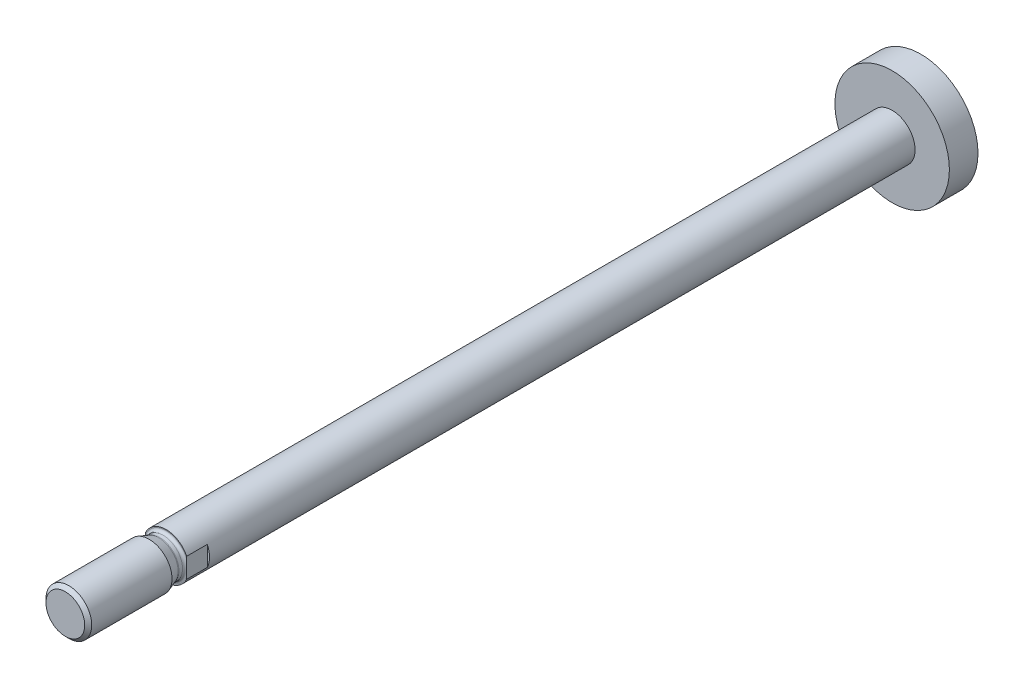
SolidWorks part; units mm, degrees
ref_plane "Ebene vorne" through (0, 0, 0) normal (0, 0, 1) x (1, 0, 0)
ref_plane "Ebene oben" through (0, 0, 0) normal (0, 1, 0) x (1, 0, 0)
ref_plane "Ebene rechts" through (0, 0, 0) normal (1, 0, 0) x (0, 0, -1)
sketch "Skizze1" plane through (0, 0, 0) normal (1, 0, 0) x (0, 0, -1)
  line L0 (-6, 0) -> (-6, 5)
  line L1 (-6, 5) -> (152.6, 5)
  line L2 (152.6, 5) -> (152.6, 12.5)
  line L3 (152.6, 12.5) -> (158.85, 12.5)
  line L4 (158.85, 12.5) -> (158.85, 0)
  line L5 (158.85, 0) -> (-6, 0)
  line L6 (158.85, 0) -> (-6, 0) construction
revolve "Rotation1" add sketch "Skizze1" angle 360 about L6 reverse direction yes
sketch "Skizze2" plane through (0, 0, 0) normal (1, 0, 0) x (0, 0, -1)
  line L0 (-28, 0) -> (-28, 4.233)
  line L1 (-28, 4.233) -> (-27.233, 5)
  line L2 (-27.233, 5) -> (-9.698, 5)
  line L3 (-9.698, 5) -> (-7.5994, 4.2362)
  line L4 (-7.3942, 4.2) -> (-6.6, 4.2)
  line L5 (-6, 4.8) -> (-6, 5)
  line L6 (-6, 5) -> (-5, 5)
  line L7 (-5, 5) -> (-5, 0)
  line L8 (-5, 0) -> (-28, 0)
  line L9 (-5, 0) -> (-28, 0) construction
  arc A0 (-7.5994, 4.2362) -> (-7.3942, 4.2) centre (-7.3942, 4.8) ccw
  arc A1 (-6.6, 4.2) -> (-6, 4.8) centre (-6.6, 4.8) ccw
revolve "Rotation2" add sketch "Skizze2" angle 360 about L9 reverse direction yes
cosmetic thread "Gewindedarstellung1" parameters "D1"=18.302, "D2"=8.466
ref_plane "Ebene1" through (0, 0, 6) normal (0, 0, 1) x (1, 0, 0)
ref_plane "Ebene2" through (0, 0, 1.5) normal (0, 0, 1) x (1, 0, 0)
sketch "Skizze3" plane through (0, 0, 1.5) normal (0, 0, 1) x (1, 0, 0)
  line L0 (-9, 18) -> (-9, -9)
  line L1 (-9, -9) -> (-4.5, -9)
  line L2 (-4.5, -9) -> (-4.5, 9)
  line L3 (-4.5, 9) -> (4.5, 9)
  line L4 (4.5, 9) -> (4.5, -9)
  line L5 (4.5, -9) -> (9, -9)
  line L6 (9, -9) -> (9, 18)
  line L7 (9, 18) -> (-9, 18)
extrude "Schnitt-Linear austragen1" cut sketch "Skizze3" along normal blind 5.5
ref_plane "Ebene3" through (0, 0, -319.5) normal (0, 0, 1) x (1, 0, 0)
ref_plane "Ebene4" through (0, 0, 17.667) normal (0, 0, 1) x (1, 0, 0)
ref_plane "Ebene5" through (0, 0, 15) normal (0, 0, 1) x (1, 0, 0)
ref_plane "FDT_KSAUFSATZ XY" through (0, 0, 15) normal (0, 0, 1) x (1, 0, 0)
ref_plane "FDT_KSAUFSATZ XZ" through (0, 0, 0) normal (0, 1, 0) x (1, 0, 0)
ref_plane "FDT_KSAUFSATZ YZ" through (0, 0, 0) normal (-1, 0, 0) x (0, 0, 1)
ref_axis "FDT_KSAUFSATZ X" through (80.9, 0, 15) along (-1, 0, 0)
ref_axis "FDT_KSAUFSATZ Y" through (0, 50, 15) along (0, -1, 0)
ref_axis "FDT_KSAUFSATZ Z" through (0, 0, 80.9) along (0, 0, -1)
sketch3d "FDT_KSAUFSATZ"
  point P0 (0, 0, 15)
ref_plane "FDT_NUT XY" through (0, 0, 15) normal (0, 0, 1) x (1, 0, 0)
ref_plane "FDT_NUT XZ" through (0, 0, 0) normal (0, 1, 0) x (1, 0, 0)
ref_plane "FDT_NUT YZ" through (0, 0, 0) normal (-1, 0, 0) x (0, 0, 1)
ref_axis "FDT_NUT X" through (80.9, 0, 15) along (-1, 0, 0)
ref_axis "FDT_NUT Y" through (0, 50, 15) along (0, -1, 0)
ref_axis "FDT_NUT Z" through (0, 0, 80.9) along (0, 0, -1)
sketch3d "FDT_NUT"
  point P0 (0, 0, 15)
ref_plane "KS XY" through (0, 0, 0) normal (0, 0, -1) x (-1, 0, 0)
ref_plane "KS XZ" through (0, 0, 0) normal (0, 1, 0) x (1, 0, 0)
ref_plane "KS YZ" through (0, 0, 0) normal (1, 0, 0) x (0, 0, -1)
ref_axis "KS X" through (-80.9, 0, 0) along (1, 0, 0)
ref_axis "KS Y" through (0, 50, 0) along (0, -1, 0)
ref_axis "KS Z" through (0, 0, -80.9) along (0, 0, 1)
sketch3d "KS"
  point P0 (0, 0, 0)
ref_plane "NUT1 XY" through (0, 0, 17.667) normal (0, 0, 1) x (1, 0, 0)
ref_plane "NUT1 XZ" through (0, 0, 0) normal (0, -1, 0) x (-1, 0, 0)
ref_plane "NUT1 YZ" through (0, 0, 0) normal (1, 0, 0) x (0, 0, -1)
ref_axis "NUT1 X" through (-80.9, 0, 17.667) along (1, 0, 0)
ref_axis "NUT1 Y" through (0, -50, 17.667) along (0, 1, 0)
ref_axis "NUT1 Z" through (0, 0, 80.9) along (0, 0, -1)
sketch3d "NUT1"
  point P0 (0, 0, 17.667)
sketch "Sketch1" plane through (0, 0, 0) normal (1, 0, 0) x (0, 0, -1)
  point P0 (-36, 0)
  dimension "D1" = 36
